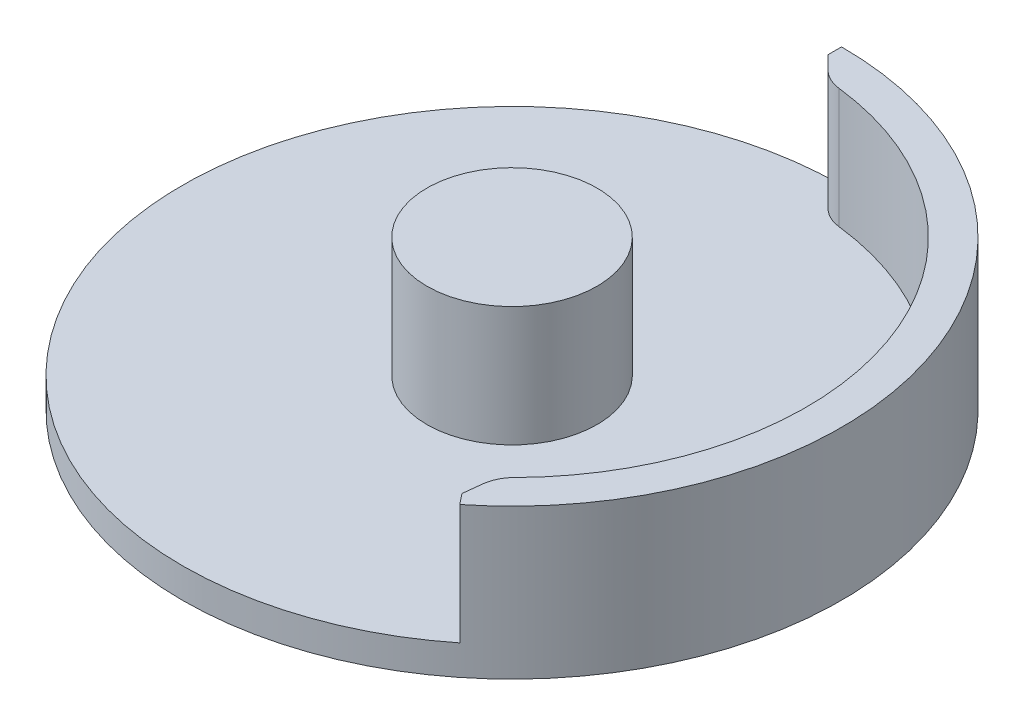
SolidWorks part; units mm, degrees
ref_plane "Front Plane" through (0, 0, 0) normal (0, 0, 1) x (1, 0, 0)
ref_plane "Top Plane" through (0, 0, 0) normal (0, 1, 0) x (1, 0, 0)
ref_plane "Right Plane" through (0, 0, 0) normal (1, 0, 0) x (0, 0, -1)
sketch "Sketch1" plane through (0, 0, 0) normal (0, 1, 0) x (1, 0, 0)
  circle A0 centre (0, 0) radius 27.5
  dimension "D1" = 55
extrude "Boss-Extrude1" add sketch "Sketch1" along normal blind 2.5
sketch "Sketch2" plane through (0, 2.5, 0) normal (0, 1, 0) x (1, 0, 0)
  circle A0 centre (0, 0) radius 7.1
  dimension "D1" = 14.2
extrude "Boss-Extrude2" add sketch "Sketch2" along normal blind 10
sketch "Sketch3" plane through (0, 2.5, 0) normal (0, 1, 0) x (1, 0, 0)
  circle A0 centre (0, 0) radius 24.57
  dimension "D1" = 49.14
sketch "Sketch5" plane through (0, 2.5, 0) normal (0, 1, 0) x (1, 0, 0)
  line L0 (0, 24.57) -> (0, 27.5)
  line L1 (15.3168, -19.2115) -> (17.1433, -21.5025)
  arc A0 (0, 24.57) -> (15.3168, -19.2115) centre (0, 0) cw
  circle A1 centre (0, 0) radius 24.57 construction
  circle A2 centre (0, 0) radius 27.5 construction
  arc A3 (0, 27.5) -> (17.1433, -21.5025) centre (0, 0) cw
extrude "Boss-Extrude3" add sketch "Sketch5" along normal blind 10
chamfer "Chamfer1" distance 1.8 angle 45 2 edges at (15.3168, 7.5, 19.2115) (0, 7.5, -24.57)
fillet "Fillet2" radius 3 2 edges at (16.7355, 7.5, 17.9891) (1.8714, 7.5, -24.4986)
